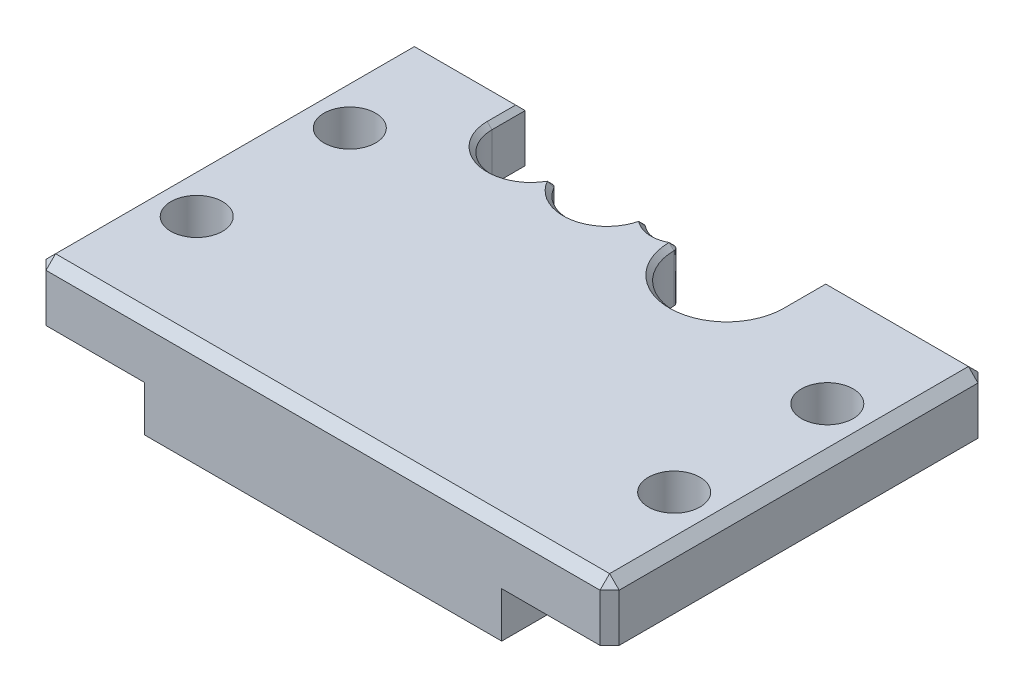
SolidWorks part; units mm, degrees
ref_plane "Front Plane" through (0, 0, 0) normal (0, 0, 1) x (1, 0, 0)
ref_plane "Top Plane" through (0, 0, 0) normal (0, 1, 0) x (1, 0, 0)
ref_plane "Right Plane" through (0, 0, 0) normal (1, 0, 0) x (0, 0, -1)
sketch "Sketch1" plane through (0, 0, 0) normal (0, 0, 1) x (1, 0, 0)
  point P0 (0, 0)
  line B0 (18.87, 0) -> (-18.87, 0) construction
  line B1 (23.1, 46.5001) -> (23.1, 59.75) construction
  line B2 (23.1, 59.75) -> (18.87, 59.75) construction
  line B3 (18.87, 59.75) -> (18.87, 0) construction
  line B4 (18.87, 0) -> (29.95, 0) construction
  line B5 (29.95, 0) -> (29.95, 39.05) construction
  line B6 (29.95, 39.05) -> (27.2, 40.8) construction
  line B7 (27.2, 40.8) -> (27.2, 46.5001) construction
  line B8 (27.2, 46.5001) -> (23.1, 46.5001) construction
  line B9 (-23.1, 59.75) -> (-23.1, 46.5001) construction
  line B10 (-23.1, 46.5001) -> (-27.2, 46.5001) construction
  line B11 (-27.2, 46.5001) -> (-27.2, 40.8) construction
  line B12 (-27.2, 40.8) -> (-29.95, 39.05) construction
  line B13 (-29.95, 39.05) -> (-29.95, 0) construction
  line B14 (-29.95, 0) -> (-18.87, 0) construction
  line B15 (-18.87, 0) -> (-18.87, 59.75) construction
  line B16 (-18.87, 59.75) -> (-23.1, 59.75) construction
  circle B17 centre (-24.95, 25.5) radius 2.95 construction
  circle B18 centre (-24.95, 9.5) radius 2.95 construction
  circle B19 centre (24.95, 9.5) radius 2.95 construction
  circle B20 centre (24.95, 25.5) radius 2.95 construction
sketch_block_instance "Block1-1"
sketch_block "Block1"
sketch "Sketch2" plane through (0, 0, 0) normal (0, 1, 0) x (1, 0, 0)
  point P0 (0, 0)
  line B0 (-29.95, 39.5) -> (-29.95, 0) construction
  line B1 (-29.95, 0) -> (-18.87, 0) construction
  line B2 (-18.87, 0) -> (-18.87, 39.5) construction
  line B3 (-18.87, 39.5) -> (-29.95, 39.5) construction
  line B4 (29.95, 0) -> (29.95, 39.5) construction
  line B5 (29.95, 39.5) -> (18.87, 39.5) construction
  line B6 (18.87, 39.5) -> (18.87, 0) construction
  line B7 (18.87, 0) -> (29.95, 0) construction
  line B8 (-18.87, 0) -> (18.87, 0) construction
  circle B9 centre (24.95, 27.75) radius 2.95 construction
  circle B10 centre (-24.95, 11.75) radius 2.95 construction
  circle B11 centre (-24.95, 27.75) radius 2.95 construction
  circle B12 centre (24.95, 11.75) radius 2.95 construction
sketch_block_instance "Block2-1"
sketch_block "Block2"
sketch "Sketch3" plane through (0, 0, 0) normal (0, 1, 0) x (1, 0, 0)
  line L0 (-18.87, 0) -> (18.87, 0) construction
  line L1 (-18.675, 0) -> (18.675, 0)
  line L2 (-18.675, 0) -> (-18.675, 6)
  line L3 (-18.675, 6) -> (18.675, 6)
  line L4 (18.675, 0) -> (18.675, 6)
  line L5 (0, 6) -> (0, 0) construction
  line L6 (-18.675, 3) -> (18.675, 3) construction
  point P148 (0, 3)
  dimension "D1" = 37.35
  dimension "D2" = 6
extrude "Boss-Extrude1" add sketch "Sketch3" along normal blind 4.75
sketch "Sketch4" plane through (0, 0, 0) normal (0, 1, 0) x (1, 0, 0)
  line L1 (-29.95, 0) -> (29.95, 0)
  line L2 (-29.95, 0) -> (-29.95, 39.5)
  line L3 (-29.95, 39.5) -> (29.95, 39.5)
  line L4 (29.95, 0) -> (29.95, 39.5)
  line L5 (0, 39.5) -> (0, 0) construction
  line L6 (-29.95, 19.75) -> (29.95, 19.75) construction
  circle A0 centre (-24.95, 11.75) radius 2.7
  circle A1 centre (-24.95, 27.75) radius 2.7
  circle A2 centre (24.95, 11.75) radius 2.7
  circle A3 centre (24.95, 27.75) radius 2.7
  point P168 (0, 19.75)
  dimension "D1" = 5.4
extrude "Boss-Extrude2" add sketch "Sketch4" against normal blind 6
sketch "Sketch5" plane through (0, -6, 0) normal (0, -1, 0) x (1, 0, 0)
  line L0 (29.95, -39.5) -> (-29.95, -39.5) construction
  line L2 (-18.87, 0) -> (-18.87, -39.5) construction
  line L6 (-17.87, -35.525) -> (-17.87, -39.5)
  line L7 (-17.87, -39.5) -> (13.5362, -39.5)
  line L8 (13.5362, -34.125) -> (13.5362, -39.5)
  circle A0 centre (-13.795, -35.525) radius 3.975 construction
  circle A1 centre (-5.845, -35.525) radius 3.975 construction
  circle A2 centre (0.5846, -36.9) radius 2.6 construction
  circle A3 centre (8.0612, -34.125) radius 5.375 construction
  arc A4 (13.5362, -34.125) -> (2.5864, -34.0786) centre (8.0612, -34.125) ccw
  arc A5 (1.8518, -34.5158) -> (-1.0991, -34.7893) centre (0.5846, -36.9) ccw
  arc A6 (-1.8955, -34.5215) -> (-9.3856, -33.5076) centre (-5.845, -35.525) ccw
  arc A7 (-10.2544, -33.5076) -> (-17.87, -35.525) centre (-13.795, -35.525) ccw
  circle A8 centre (8.0612, -34.125) radius 5.475 construction
  circle A9 centre (0.5846, -36.9) radius 2.7 construction
  circle A10 centre (-5.845, -35.525) radius 4.075 construction
  circle A11 centre (-13.795, -35.525) radius 4.075 construction
  arc A12 (-10.2544, -33.5076) -> (-9.3856, -33.5076) centre (-9.82, -33.26) ccw
  arc A13 (-1.8955, -34.5215) -> (-1.0991, -34.7893) centre (-1.4109, -34.3984) ccw
  arc A14 (2.5864, -34.0786) -> (1.8518, -34.5158) centre (2.0865, -34.0743) cw
  dimension "D1" = 7.95
  dimension "D2" = 7.95
  dimension "D3" = 10.75
  dimension "D6" = 0.5
  dimension "D7" = 0.5
  dimension "D8" = 0.5
  dimension "D10" = 5.2
  dimension "D9" = 1
  dimension "D4" = 0.1
  dimension "D5" = 0.1
extrude "Cut-Extrude1" cut sketch "Sketch5" against normal up to next
chamfer "Chamfer1" distance 1 angle 45 9 edges at (-29.95, -3, 0) (-29.95, -3, -39.5) (29.95, -3, -39.5) (29.95, -3, 0) (-23.91, -6, -39.5) (21.7431, -6, -39.5) (29.95, -6, -19.75) (0, -6, 0) (-29.95, -6, -19.75)
chamfer "Chamfer2" distance 0.5 angle 45 20 edges at (13.5362, 0, -36.8125) (8.0845, 0, -28.65) (2.3422, 0, -34.504) (0.3355, 0, -34.2115) (-1.5702, 0, -34.8723) (-5.2983, 0, -31.4868) (-9.82, 0, -33.76) (-14.8385, 0, -31.5859) (-17.87, 0, -37.5125) (13.5362, -6, -36.3125) (8.0845, -6, -28.65) (2.3422, -6, -34.504) (0.3355, -6, -34.2115) (-1.5702, -6, -34.8723) (-5.2983, -6, -31.4868) (-9.82, -6, -33.76) (-14.8385, -6, -31.5859) (-17.87, -6, -37.0125) (13.5362, -2.5, -39.5) (-17.87, -2.5, -39.5)
mirror "Mirror1" about plane through (0, -6, 0) normal (0, -1, 0) of bodies 103
delete or keep bodies "Body-Delete/Keep 1" type delete bodies bodies 103
